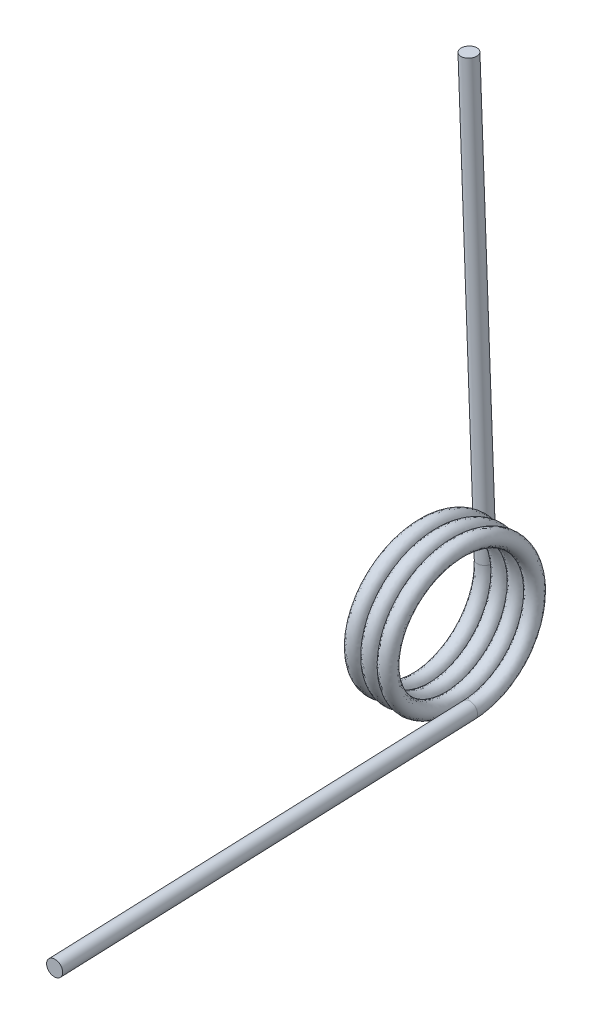
SolidWorks part; units mm, degrees
ref_plane "Front" through (0, 0, 0) normal (0, 0, 1) x (1, 0, 0)
ref_plane "Top" through (0, 0, 0) normal (0, 1, 0) x (1, 0, 0)
ref_plane "Right" through (0, 0, 0) normal (1, 0, 0) x (0, 0, -1)
sketch "Sketch1" plane through (0, 0, 0) normal (1, 0, 0) x (0, 0, -1)
  line L0 (0, 0) -> (0, -1.8034) construction
  line L1 (0, -1.8034) -> (0, -2.032) construction
  line L2 (0, -2.032) -> (0, -2.2606) construction
  circle A0 centre (0, 0) radius 1.8034 construction
  circle A1 centre (0, 0) radius 2.2606 construction
  circle A2 centre (0, 0) radius 2.032
  circle A3 centre (0, -2.032) radius 0.2286 construction
  circle A4 centre (0, 0) radius 1.3843 construction
  dimension "Wire Dia" = 0.4572
curve "Helix/Spiral1" pitch 0.4826 height 1.5684 radius 2.032 left hand yes centre (0, 0, 0) axis (1, 0, 0) start towards (0, 0, -1)
ref_plane "Plane1" through (0, 0, -2.032) normal (0.0378, -0.9993, 0) x (0.9993, 0.0378, 0)
sketch "Sketch2" plane through (0, 0, -2.032) normal (0.0378, -0.9993, 0) x (0.9993, 0.0378, 0)
  circle A0 centre (0, 0) radius 0.2286
  dimension "D1" = 0.4572
sweep "Sweep1" add profiles "Sketch2" path "Helix/Spiral1"
sketch "Sketch3" plane through (0, 0, 0) normal (-0.0378, 0.9993, 0) x (-0.9993, -0.0378, 0)
  circle A1 centre (0, -2.032) radius 0.2286
  circle A2 centre (0, -2.032) radius 0.2286
  dimension "D1" = 0
extrude "Extrude1" add sketch "Sketch3" along normal blind 12.7
sketch "Sketch4" plane through (0.0022, 0, 0.0592) normal (0.0378, 0, 0.9993) x (0.9993, 0, -0.0378)
  circle A1 centre (1.5673, -2.032) radius 0.2286
  circle A2 centre (1.5673, -2.032) radius 0.2286
  dimension "D1" = 0
extrude "Extrude2" add sketch "Sketch4" along normal blind 12.7
sketch "Sketch5" plane through (0, 0, 0) normal (1, 0, 0) x (0, 0, -1)
  circle A0 centre (0, 0) radius 1.3843 construction
  circle A1 centre (0, 0) radius 1.3843
equation "\"D4@Helix/Spiral1\"=\"Wire Dia@Sketch1\"+.001"
equation "\"D1@Sketch2\"=\"Wire Dia@Sketch1\""
equation "\"D1@Extrude2\"=\"Leg Length@Extrude1\""
